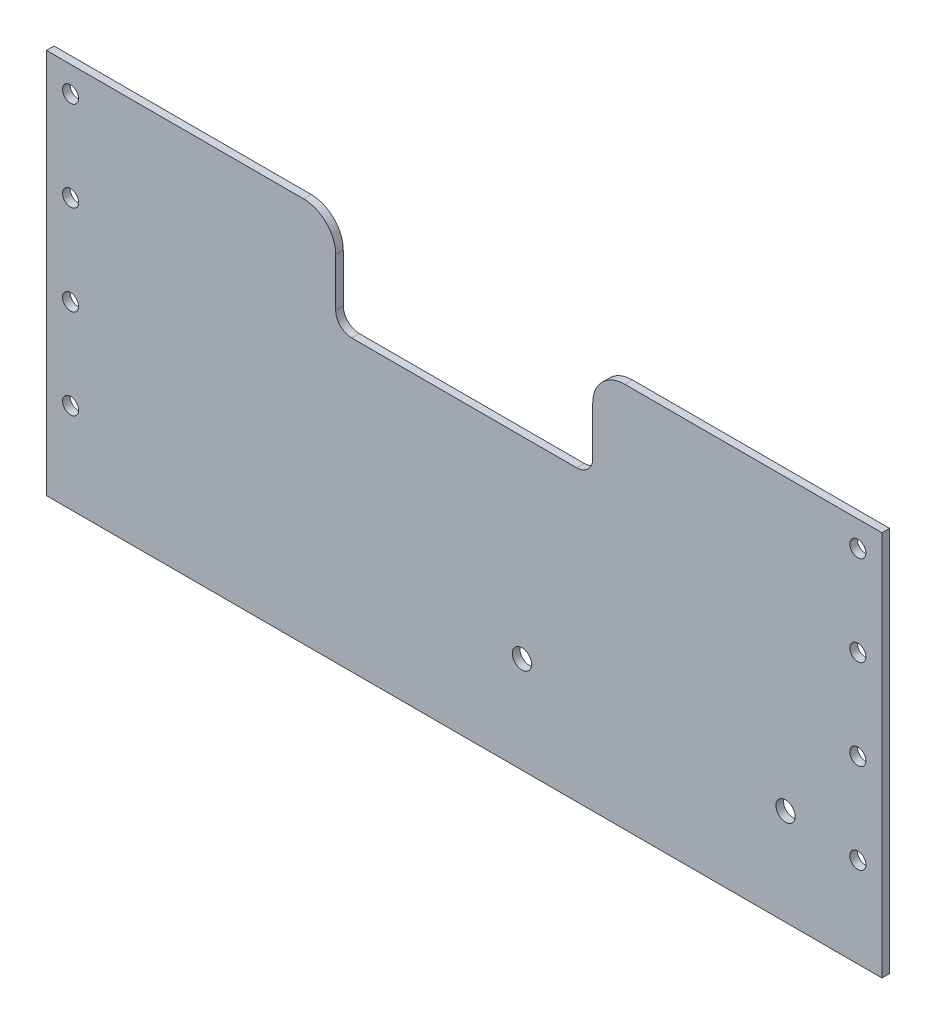
SolidWorks part; units mm, degrees
material "Thornel VCB-20 Carbon Cloth"
ref_plane "Front Plane" through (0, 0, 0) normal (0, 0, 1) x (1, 0, 0)
ref_plane "Top Plane" through (0, 0, 0) normal (0, 1, 0) x (1, 0, 0)
ref_plane "Right Plane" through (0, 0, 0) normal (1, 0, 0) x (0, 0, -1)
sketch "Sketch1" plane through (0, 0, 0) normal (0, 0, 1) x (1, 0, 0)
  line L0 (0, -58.42) -> (0, 58.42) construction
  line L2 (-82.55, 55.7897) -> (-82.55, -52.07)
  line L3 (-76.2, -58.42) -> (76.2, -58.42)
  line L4 (82.55, 55.7897) -> (82.55, -52.07)
  line L5 (-82.55, 58.42) -> (82.55, -58.42) construction
  line L6 (-82.55, -58.42) -> (82.55, 58.42) construction
  line L7 (-80.6901, 60.2799) -> (-75.4296, 65.5404)
  line L8 (-70.9395, 67.4003) -> (-50.8, 67.4003)
  line L9 (-46.3099, 65.5404) -> (-41.0494, 60.2799)
  line L10 (46.3099, 65.5404) -> (41.0494, 60.2799)
  line L11 (70.9395, 67.4003) -> (50.8, 67.4003)
  line L12 (80.6901, 60.2799) -> (75.4296, 65.5404)
  line L13 (-73.5697, 67.4003) -> (-82.55, 67.4003) construction
  line L14 (-82.55, 67.4003) -> (-82.55, 58.42) construction
  line L15 (-36.5592, 58.42) -> (0, 58.42)
  line L16 (0, 58.42) -> (36.5592, 58.42)
  circle A0 centre (-77.7875, -35.052) radius 1.5875
  circle A1 centre (-77.7875, -11.684) radius 1.5875
  circle A2 centre (-77.7875, 11.684) radius 1.5875
  circle A3 centre (-77.7875, 35.052) radius 1.5875
  circle A4 centre (77.7875, 35.052) radius 1.5875
  circle A5 centre (77.7875, 11.684) radius 1.5875
  circle A6 centre (77.7875, -11.684) radius 1.5875
  circle A7 centre (77.7875, -35.052) radius 1.5875
  arc A8 (82.55, 55.7897) -> (80.6901, 60.2799) centre (76.2, 55.7897) ccw
  arc A9 (75.4296, 65.5404) -> (70.9395, 67.4003) centre (70.9395, 61.0503) ccw
  arc A10 (46.3099, 65.5404) -> (50.8, 67.4003) centre (50.8, 61.0503) cw
  arc A11 (41.0494, 60.2799) -> (36.5592, 58.42) centre (36.5592, 64.77) cw
  arc A12 (-36.5592, 58.42) -> (-41.0494, 60.2799) centre (-36.5592, 64.77) cw
  arc A13 (-46.3099, 65.5404) -> (-50.8, 67.4003) centre (-50.8, 61.0503) ccw
  arc A14 (-70.9395, 67.4003) -> (-75.4296, 65.5404) centre (-70.9395, 61.0503) ccw
  arc A15 (-82.55, 55.7897) -> (-80.6901, 60.2799) centre (-76.2, 55.7897) cw
  arc A16 (76.2, -58.42) -> (82.55, -52.07) centre (76.2, -52.07) ccw
  arc A17 (-76.2, -58.42) -> (-82.55, -52.07) centre (-76.2, -52.07) cw
  circle A18 centre (-70.9395, 61.0503) radius 1.5875
  circle A19 centre (-50.8, 61.0503) radius 1.5875
  circle A20 centre (50.8, 61.0503) radius 1.5875
  circle A21 centre (70.9395, 61.0503) radius 1.5875
  point P0 (0, 0)
  point P36 (73.5697, 67.4003)
  point P39 (48.1697, 67.4003)
  point P42 (39.1895, 58.42)
  point P45 (-39.1895, 58.42)
  point P48 (-48.1697, 67.4003)
  dimension "D3" = 3.175
  dimension "D11" = 6.35
  dimension "D12" = 6.35
  dimension "D13" = 3.175
  dimension "D14" = 3.175
  dimension "D1" = 165.1
  dimension "D2" = 116.84
  dimension "D4" = 23.368
  dimension "D5" = 4.7625
  dimension "D7" = 46.736
  dimension "D8" = 12.7
  dimension "D9" = 135
  dimension "D10" = 25.4
  dimension "D6" = 4
extrude "Boss-Extrude1" [suppressed] add sketch "Sketch1" along normal blind 1.5
sketch "Sketch2" [suppressed] plane through (0, 0, 1.5) normal (0, 0, 1) x (1, 0, 0)
  line L0 (0, -45.72) -> (0, 6.3634) construction
  line L1 (0, -58.42) -> (0, 63.5) construction
  line L3 (-82.55, 1.8599) -> (82.55, 1.8599) construction
  line L4 (-82.55, 55.7897) -> (-82.55, -52.07) construction
  line L5 (82.55, -52.07) -> (82.55, 55.7897) construction
  line L7 (-76.2, -58.42) -> (76.2, -58.42) construction
  circle A0 centre (0, -45.72) radius 1.9062
  circle A1 centre (0, 6.3634) radius 1.9062
  dimension "D2" = 3.8125
  dimension "D3" = 3.8125
  dimension "D1" = 52.0834
  dimension "D4" = 12.7
extrude "Cut-Extrude1" [suppressed] cut sketch "Sketch2" against normal through all
sketch "Sketch3" [suppressed] plane through (0, 0, 1.5) normal (0, 0, 1) x (1, 0, 0)
  line L0 (0, 50.8) -> (0, 30.8) construction
  line L1 (-10, 40.8) -> (10, 40.8) construction
  line L2 (-10, 40.8) -> (0, 50.8) construction
  line L3 (0, 50.8) -> (10, 40.8) construction
  line L4 (10, 40.8) -> (0, 30.8) construction
  line L5 (0, 30.8) -> (-10, 40.8) construction
  line L6 (0, 63.5) -> (0, -58.42) construction
  line L8 (-76.2, -58.42) -> (76.2, -58.42) construction
  circle A0 centre (0, 50.8) radius 1.8669
  circle A1 centre (-10, 40.8) radius 1.8669
  circle A2 centre (0, 30.8) radius 1.8669
  circle A3 centre (10, 40.8) radius 1.8669
  dimension "D1" = 3.7338
  dimension "D2" = 12.7
extrude "Cut-Extrude2" [suppressed] cut sketch "Sketch3" against normal through all
sketch "Sketch4" [suppressed] plane through (0, 0, 1.5) normal (0, 0, 1) x (1, 0, 0)
  line L0 (0, 58.42) -> (0, -58.42) construction
  line L1 (36.5592, 58.42) -> (-36.5592, 58.42) construction
  line L2 (-76.2, -58.42) -> (76.2, -58.42) construction
  line L5 (0, 33.045) -> (0, 52.045) construction
  line L6 (-9.5, 42.545) -> (9.5, 42.545) construction
  circle A14 centre (0, 42.545) radius 8 construction
  circle A15 centre (0, 42.545) radius 9.5 construction
  circle A16 centre (0, 50.545) radius 1.5
  circle A17 centre (0, 34.545) radius 1.5
  circle A18 centre (-9.5, 42.545) radius 1.5
  circle A19 centre (9.5, 42.545) radius 1.5
  dimension "D1" = 15.875
  dimension "D3" = 16
  dimension "D4" = 19
  dimension "D5" = 3
  dimension "D6" = 3
  dimension "D7" = 3
  dimension "D8" = 3
extrude "Cut-Extrude3" [suppressed] cut sketch "Sketch4" against normal through all
sketch "Sketch5" plane through (0, 0, 0) normal (0, 0, 1) x (1, 0, 0)
  line L0 (0, -58.337) -> (0, 30.563) construction
  line L1 (-43.2483, 30.563) -> (43.2483, 30.563) construction
  line L2 (-82.55, 17.863) -> (-82.55, -58.337)
  line L3 (-82.55, -58.337) -> (82.55, -58.337)
  line L4 (82.55, 17.863) -> (82.55, -58.337)
  line L5 (-43.2483, 30.563) -> (82.55, -58.337) construction
  line L6 (-82.55, -58.337) -> (43.2483, 30.563) construction
  line L7 (-77.7875, -58.337) -> (-77.7875, 30.563) construction
  line L8 (-77.7875, -40.557) -> (-77.7875, -22.777) construction
  line L9 (77.7875, -58.337) -> (77.7875, 30.563) construction
  line L11 (11.4166, -39.287) -> (63.5, -39.287) construction
  line L13 (-82.55, -0.6801) -> (82.55, -0.6801) construction
  line L14 (-82.55, 17.863) -> (-31.75, 17.863)
  line L15 (-22.225, -1.187) -> (22.225, -1.187)
  line L16 (-25.4, 1.988) -> (-25.4, 11.513)
  line L17 (25.4, 1.988) -> (25.4, 11.513)
  line L18 (31.75, 17.863) -> (82.55, 17.863)
  circle A0 centre (-77.7875, -40.557) radius 1.5875
  circle A1 centre (-77.7875, -22.777) radius 1.5875
  circle A2 centre (-77.7875, -4.997) radius 1.5875
  circle A3 centre (-77.7875, 12.783) radius 1.5875
  circle A8 centre (11.4166, -39.287) radius 1.9062
  circle A9 centre (63.5, -39.287) radius 1.9062
  circle A10 centre (21.1667, -9.332) radius 1.5875 construction
  circle A11 centre (-21.1667, -9.332) radius 1.5875 construction
  arc A12 (-25.4, 11.513) -> (-31.75, 17.863) centre (-31.75, 11.513) ccw
  arc A13 (25.4, 11.513) -> (31.75, 17.863) centre (31.75, 11.513) cw
  arc A14 (25.4, 1.988) -> (22.225, -1.187) centre (22.225, 1.988) cw
  arc A15 (-25.4, 1.988) -> (-22.225, -1.187) centre (-22.225, 1.988) ccw
  circle A16 centre (77.7875, 12.783) radius 1.5875
  circle A17 centre (77.7875, -4.997) radius 1.5875
  circle A18 centre (77.7875, -22.777) radius 1.5875
  circle A19 centre (77.7875, -40.557) radius 1.5875
  point P0 (0, 0)
  point P35 (0, 0)
  point P52 (25.4, 17.863)
  point P55 (25.4, -1.187)
  point P58 (-25.4, -1.187)
  point P59 (0, -1.187)
  dimension "D6" = 4
  dimension "D4" = 3.175
  dimension "D12" = 3.175
  dimension "D13" = 3.175
  dimension "D17" = 6.35
  dimension "D18" = 6.35
  dimension "D19" = 3.175
  dimension "D20" = 3.175
  dimension "D22" = 3.8125
  dimension "D23" = 3.8125
  dimension "D2" = 165.1
  dimension "D3" = 4.7625
  dimension "D5" = 17.78
  dimension "D7" = 17.78
  dimension "D8" = 39.895
  dimension "D9" = 39.895
  dimension "D10" = 61.3833
  dimension "D11" = 61.3833
  dimension "D14" = 12.7
  dimension "D15" = 50.8
  dimension "D16" = 19.05
  dimension "D21" = 52.0834
  dimension "D25" = 88.9
  dimension "D24" = 19.05
  dimension "D26" = 19.05
extrude "Boss-Extrude2" add sketch "Sketch5" along normal blind 1.5
equation "\"Top Plate Width\" = 4.5in"
equation "\"Plate Width\" = 3.5in"
equation "\"Plate Thickness\" = 0.375in"
equation "\"Num holes\" = 4"
equation "\"Plate Height\" = 1.25in"
equation "\"Plate Clearance Hole Diameter\" = 0.125in"
equation "\"D3@Sketch1\"=\"Plate Clearance Hole Diameter\""
equation "\"Hole Spacing\"= \"Plate Width\" / ( \"Num holes\" + 1 )"
equation "\"Plate Tap Hole Diameter\" = 0.116in"
equation "\"Bottom Plate Length\" = 6.5in"
equation "\"D2@Sketch5\"=\"Bottom Plate Length\""
equation "\"D3@Sketch5\"=\"Plate Thickness\"/2"
equation "\"D4@Sketch5\"=\"Plate Clearance Hole Diameter\""
equation "\"D5@Sketch5\"=(\"Plate Width\" )/ ( \"Num holes\" + 1 )"
equation "\"D6@Sketch5\"=\"Num holes\""
equation "\"D7@Sketch5\"=\"Plate Width\"/ ( \"Num holes\" + 1 )"
equation "\"D12@Sketch5\"=\"Plate Clearance Hole Diameter\""
equation "\"D13@Sketch5\"=\"Plate Clearance Hole Diameter\""
equation "\"D25@Sketch5\"=\"Plate Width\""
